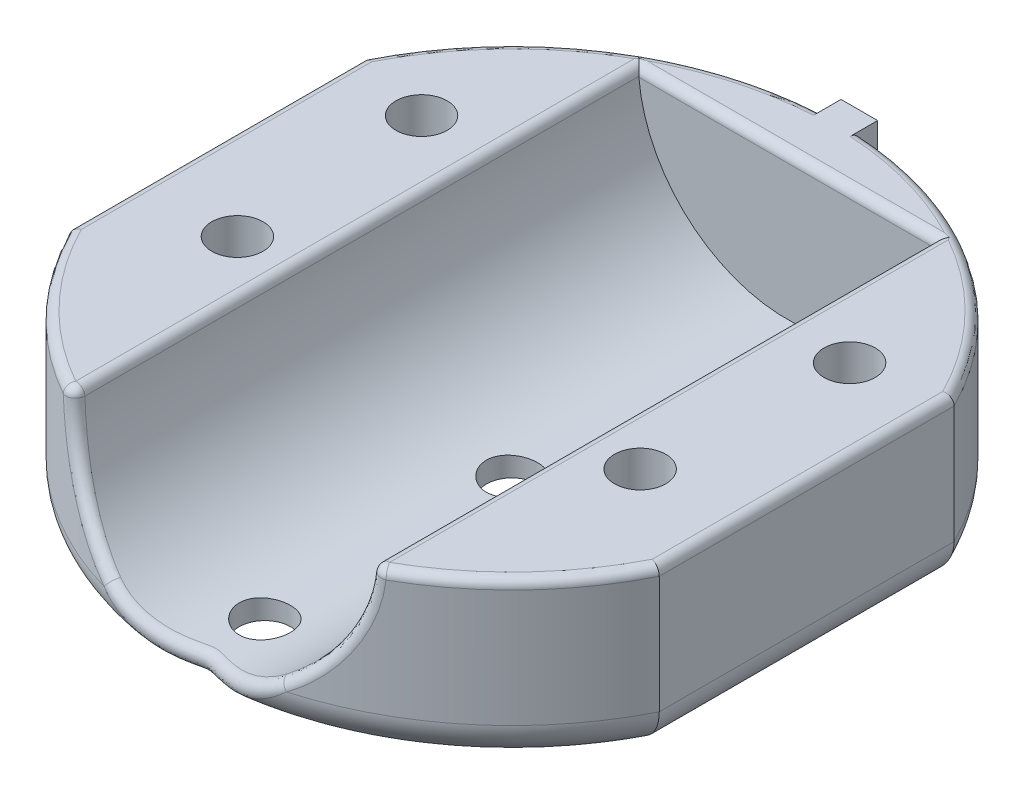
SolidWorks part; units mm, degrees
ref_plane "Front Plane" through (0, 0, 0) normal (0, 0, 1) x (1, 0, 0)
ref_plane "Top Plane" through (0, 0, 0) normal (0, 1, 0) x (1, 0, 0)
ref_plane "Right Plane" through (0, 0, 0) normal (1, 0, 0) x (0, 0, -1)
sketch "Sketch1" plane through (0, 0, 0) normal (0, 1, 0) x (1, 0, 0)
  line L0 (-1, 17.9722) -> (-1, 18.9722)
  line L1 (-1, 18.9722) -> (1, 18.9722)
  line L2 (1, 18.9722) -> (1, 17.9722)
  line L3 (0, 18.9722) -> (0, 0) construction
  arc A0 (-1, 17.9722) -> (1, 17.9722) centre (0, 0) ccw
  dimension "D1" = 36
  dimension "D2" = 2
  dimension "D3" = 1
extrude "Boss-Extrude1" add sketch "Sketch1" along normal blind 1
sketch "Sketch2" plane through (0, 0, 0) normal (0, 0, 1) x (1, 0, 0)
  line L0 (18, 1) -> (-18, 1) construction
  line L1 (0, 9.11) -> (-10.9803, 9.11) construction
  line L2 (-16.0975, 8.91) -> (-8.0975, 8.91)
  line L3 (-16.0975, 8.91) -> (-16.0975, 1)
  line L4 (8.0975, 8.91) -> (16.0975, 8.91)
  line L5 (16.0975, 8.91) -> (16.0975, 1)
  line L6 (0, 9.11) -> (0, 0) construction
  line L7 (-16.0975, 1) -> (16.0975, 1)
  circle A0 centre (0, 9.11) radius 8 construction
  arc A1 (-8.0975, 8.91) -> (8.0975, 8.91) centre (0, 9.11) ccw
  dimension "D1" = 16
  dimension "D2" = 0.1
  dimension "D3" = 0.01
  dimension "D4" = 0.2
  dimension "D5" = 8
extrude "Boss-Extrude2" add sketch "Sketch2" along normal through all and the other way through all
sketch "Sketch3" plane through (0, 0, 0) normal (0, -1, 0) x (1, 0, 0)
  line L3 (-1, -17.9722) -> (-1, -18.9722)
  line L4 (-1, -18.9722) -> (1, -18.9722)
  line L5 (1, -18.9722) -> (1, -17.9722)
  line L6 (-1, -17.9722) -> (-1, -18.9722)
  line L7 (-1, -18.9722) -> (1, -18.9722)
  line L8 (1, -18.9722) -> (1, -17.9722)
  circle A0 centre (0, 0) radius 59.9105
  arc A1 (1, -17.9722) -> (-1, -17.9722) centre (0, 0) ccw
  arc A2 (1, -17.9722) -> (-1, -17.9722) centre (0, 0) ccw
  dimension "D1" = 0
extrude "Cut-Extrude1" cut sketch "Sketch3" against normal through all
sketch "Sketch5" plane through (0, 0, 0) normal (0, 1, 0) x (1, 0, 0)
  line L0 (-11, -4) -> (11, -4) construction
  line L1 (0, -4) -> (0, 0) construction
  circle A0 centre (0, 0) radius 1.4
  circle A2 centre (11, -4) radius 1.4
  circle A4 centre (-11, -4) radius 1.4
  arc A6 (0, -14.525) -> (0, -12.475) centre (0, -13.5) ccw construction
  arc A7 (-11.6913, 7.775) -> (-11.6913, 5.725) centre (-11.6913, 6.75) ccw construction
  arc A8 (0, -14.525) -> (0, -12.475) centre (0, -13.5) ccw construction
  arc A9 (11.6913, 5.725) -> (11.6913, 7.775) centre (11.6913, 6.75) ccw construction
  arc A10 (-11.6913, 7.775) -> (-11.6913, 5.725) centre (-11.6913, 6.75) ccw construction
  arc A11 (11.6913, 5.725) -> (11.6913, 7.775) centre (11.6913, 6.75) ccw construction
  circle A13 centre (-11.6913, 6.75) radius 1.4
  circle A15 centre (0, -13.5) radius 1.4
  circle A17 centre (11.6913, 6.75) radius 1.4
  dimension "D1" = 2.8
  dimension "D2" = 2.8
  dimension "D3" = 22
  dimension "D4" = 4
extrude "Cut-Extrude2" cut sketch "Sketch5" against normal through all and the other way through all
sketch "Sketch6" plane through (0, 0, 0) normal (0, -1, 0) x (1, 0, 0)
  line L0 (-8.0975, -15) -> (8.0975, -15)
  line L1 (-8.0975, 16.0758) -> (-8.0975, -16.0758) construction
  line L2 (8.0975, 16.0758) -> (8.0975, -16.0758) construction
  line L3 (-8, -15) -> (8, -15) construction
  line L4 (-8.0975, -15) -> (-8.0975, -16.0758)
  line L5 (8.0975, -15) -> (8.0975, -16.0758)
  line L11 (8.0975, -16.0758) -> (8.0975, 16.0758)
  line L12 (1, -18.9722) -> (1, -17.9722)
  line L13 (-1, -18.9722) -> (1, -18.9722)
  line L14 (-1, -17.9722) -> (-1, -18.9722)
  line L15 (-8.0975, 16.0758) -> (-8.0975, -16.0758)
  line L17 (1, -18.9722) -> (1, -17.9722)
  line L18 (-1, -18.9722) -> (1, -18.9722)
  line L19 (-1, -17.9722) -> (-1, -18.9722)
  arc A3 (8.0975, 16.0758) -> (-8.0975, 16.0758) centre (0, 0) ccw
  arc A4 (1, -17.9722) -> (8.0975, -16.0758) centre (0, 0) ccw
  arc A5 (-8.0975, -16.0758) -> (-1, -17.9722) centre (0, 0) ccw
  arc A7 (1, -17.9722) -> (8.0975, -16.0758) centre (0, 0) ccw
  arc A8 (-8.0975, -16.0758) -> (-1, -17.9722) centre (0, 0) ccw
  dimension "D1" = 0
extrude "Boss-Extrude3" add sketch "Sketch6" against normal up to surface (8.91 mm away) up to face at (-11.6913, 8.91, -8.15)
sketch "Sketch7" plane through (0, 1, 0) normal (0, 1, 0) x (1, 0, 0)
  line L0 (16.0975, 8.0542) -> (16.0975, -8.0542) construction
  line L1 (-16.0975, -8.0542) -> (-16.0975, 8.0542) construction
  line L2 (16.0975, 8.0542) -> (16.0975, -8.0542)
  line L3 (-16.0975, -8.0542) -> (-16.0975, 8.0542)
  arc A0 (16.0975, -8.0542) -> (16.0975, 8.0542) centre (0, 0) ccw construction
  arc A1 (-16.0975, 8.0542) -> (-16.0975, -8.0542) centre (0, 0) ccw construction
  arc A2 (16.0975, -8.0542) -> (16.0975, 8.0542) centre (0, 0) ccw
  arc A3 (-16.0975, 8.0542) -> (-16.0975, -8.0542) centre (0, 0) ccw
extrude "Cut-Extrude3" cut sketch "Sketch7" against normal through all
fillet "Fillet1" radius 2 3 edges at (16.0975, 0, 0) (-16.0975, 0, 0) (0, 0, 18)
fillet "Fillet2" radius 0.5 9 edges at (7.6278, 6.3847, 16.3039) (0.6781, 1.0384, 17.7407) (-9.883, 8.91, -15.0442) (9.883, 8.91, -15.0442) (16.0975, 8.91, 0) (-12.7451, 8.91, 12.7108) (-16.0975, 8.91, 0) (0, 8.91, -15) (8.0975, 8.91, 0.5379)
